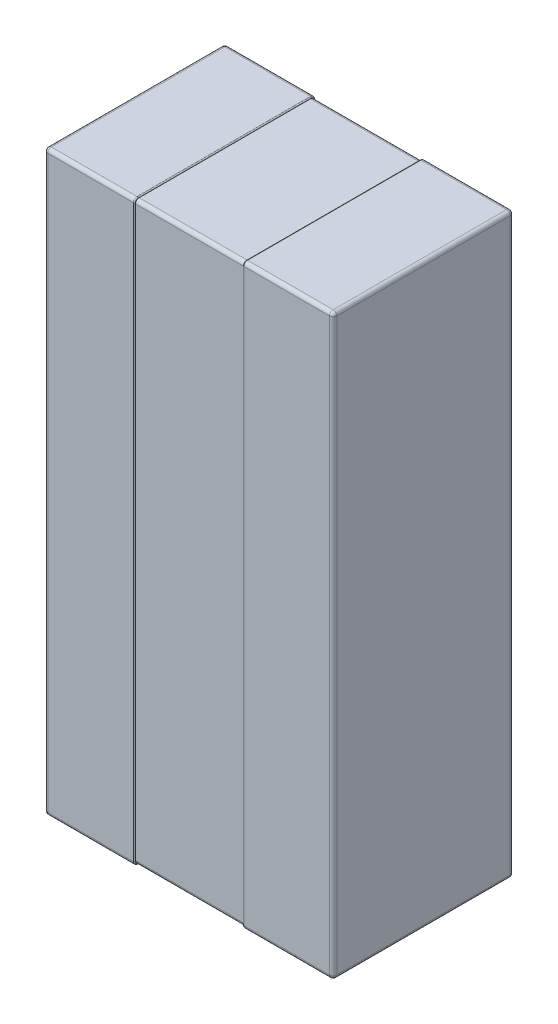
SolidWorks part; units mm, degrees
ref_plane "Top Plane" through (0, 0, 0) normal (0, 0, 1) x (1, 0, 0)
ref_plane "Front Plane" through (0, 0, 0) normal (0, 1, 0) x (1, 0, 0)
ref_plane "Side Plane" through (0, 0, 0) normal (1, 0, 0) x (0, 0, -1)
sketch "Sketch1" plane through (0, 0, 0) normal (0, 0, 1) x (1, 0, 0)
  line L1 (-0.4, 0.8) -> (0.4, 0.8)
  line L2 (-0.4, 0.8) -> (-0.4, -0.8)
  line L3 (-0.4, -0.8) -> (0.4, -0.8)
  line L4 (0.4, 0.8) -> (0.4, -0.8)
  dimension "D1" = 0.8
  dimension "D2" = 0.4
  dimension "D3" = 1.6
  dimension "D4" = 0.8
extrude "All body" add sketch "Sketch1" along normal blind 0.5
sketch "Sketch2" plane through (0, 0, 0) normal (1, 0, 0) x (0, 0, -1)
  line L14 (-0.003, 0.797) -> (-0.497, 0.797)
  line L15 (-0.003, -0.797) -> (-0.003, 0.797)
  line L16 (-0.497, -0.797) -> (-0.003, -0.797)
  line L17 (-0.497, 0.797) -> (-0.497, -0.797)
  line L18 (-0.003, 0.797) -> (-0.497, 0.797)
  line L19 (-0.003, -0.797) -> (-0.003, 0.797)
  line L20 (-0.497, -0.797) -> (-0.003, -0.797)
  line L21 (-0.497, 0.797) -> (-0.497, -0.797)
  dimension "D1" = 0.003
extrude "Cut out the body for pin" cut sketch "Sketch2" against normal blind 0.15 and the other way blind 0.15 flip side to cut
fillet "Body fillet" radius 0.01 4 edges at (0, 0.797, 0.003) (0, 0.797, 0.497) (0, -0.797, 0.003) (0, -0.797, 0.497)
fillet "Pin fillet a" radius 0.01 16 edges at (0.4, -0.8, 0.25) (0.4, 0, 0.5) (0.4, 0.8, 0.25) (0.4, 0, 0) (-0.4, 0.8, 0.25) (-0.4, 0, 0.5) (-0.4, -0.8, 0.25) (-0.4, 0, 0) (0.275, 0.8, 0.5) (0.275, -0.8, 0.5) (0.275, -0.8, 0) (0.275, 0.8, 0) (-0.275, 0.8, 0) (-0.275, -0.8, 0) (-0.275, 0.8, 0.5) (-0.275, -0.8, 0.5)
fillet "Pin fillet b" radius 0.003 16 edges at (0.15, -0.7971, 0.4971) (0.15, -0.8, 0.25) (0.15, -0.7971, 0.0029) (0.15, 0, 0) (0.15, 0.7971, 0.0029) (0.15, 0.8, 0.25) (0.15, 0.7971, 0.4971) (-0.15, -0.7971, 0.4971) (-0.15, -0.8, 0.25) (-0.15, -0.7971, 0.0029) (-0.15, 0, 0) (-0.15, 0.7971, 0.0029) (-0.15, 0.8, 0.25) (-0.15, 0.7971, 0.4971) (0.15, 0, 0.5) (-0.15, 0, 0.5)
